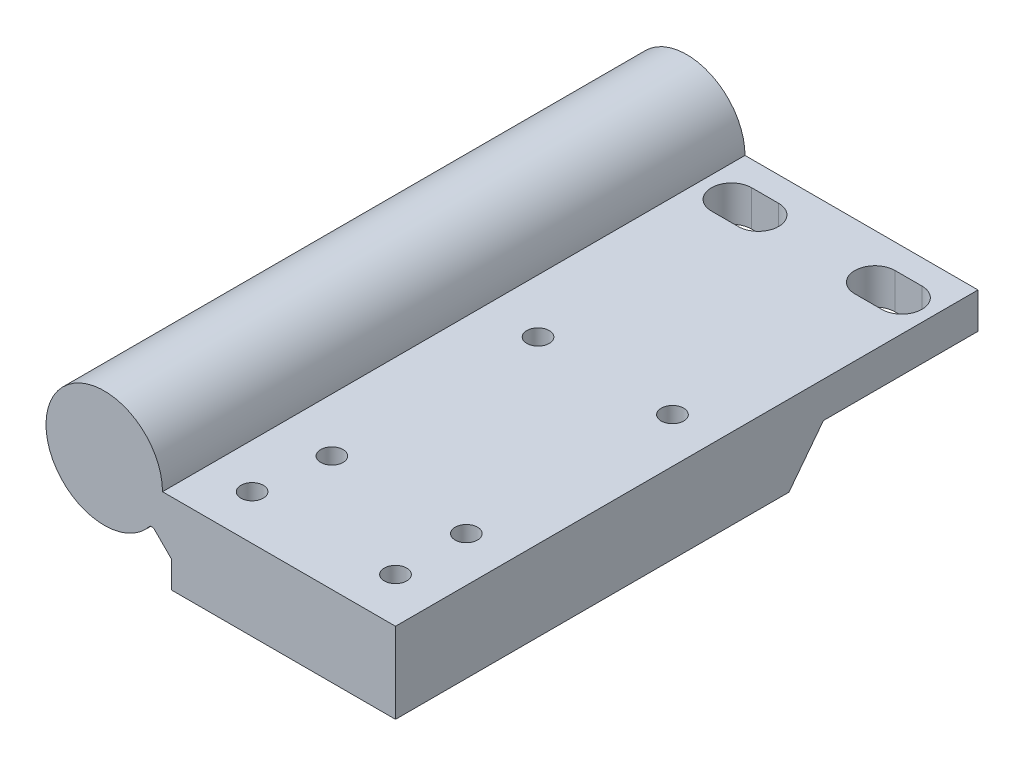
SolidWorks part; units mm, degrees
ref_plane "Спереди" through (0, 0, 0) normal (0, 0, 1) x (1, 0, 0)
ref_plane "Сверху" through (0, 0, 0) normal (0, 1, 0) x (1, 0, 0)
ref_plane "Справа" through (0, 0, 0) normal (1, 0, 0) x (0, 0, -1)
other "Configuration Table"
sketch "Эскиз1" plane through (0, 0, 0) normal (0, 0, 1) x (1, 0, 0)
  line L0 (5.1235, -4) -> (32.5, -4)
  line L1 (32.5, -4) -> (32.5, 0)
  line L2 (32.5, 0) -> (6.5, 0)
  circle A0 centre (0, 0) radius 4.1
  arc A1 (6.5, 0) -> (5.1235, -4) centre (0, 0) ccw
  circle A2 centre (39, 0) radius 6.5 construction
  dimension "D1" = 8.2
  dimension "D2" = 13
  dimension "D3" = 26
  dimension "D7" = 13
  dimension "D4" = 4
  dimension "D5" = 6.5
  dimension "D6" = 32.5
extrude "Бобышка-Вытянуть1" add sketch "Эскиз1" along normal blind 65
sketch "Эскиз2" plane through (0, 0, 65) normal (0, 0, 1) x (1, 0, 0)
  circle A0 centre (0, 0) radius 4.9232
extrude "Бобышка-Вытянуть2" add sketch "Эскиз2" against normal blind 3
sketch "Эскиз3" plane through (0, 0, 0) normal (0, 1, 0) x (1, 0, 0)
  line L0 (10, -7.25) -> (13, -7.25)
  line L1 (10, -2.75) -> (13, -2.75)
  line L6 (26, -2.75) -> (29, -2.75)
  line L7 (26, -7.25) -> (29, -7.25)
  line L8 (32.5, -65) -> (6.5, -65) construction
  line L9 (6.5, -65) -> (6.5, 0) construction
  line L11 (32.5, -65) -> (32.5, 0) construction
  arc A4 (10, -2.75) -> (10, -7.25) centre (10, -5) ccw
  arc A5 (29, -7.25) -> (29, -2.75) centre (29, -5) ccw
  arc A6 (13, -7.25) -> (13, -2.75) centre (13, -5) ccw
  arc A7 (26, -2.75) -> (26, -7.25) centre (26, -5) ccw
  circle A8 centre (11.5, -60) radius 1.25
  circle A9 centre (27.5, -60) radius 1.25
  point P23 (27.5, -7.25)
  point P25 (11.5, -7.25)
  dimension "D1" = 4.5
  dimension "D2" = 4.5
  dimension "D3" = 60
  dimension "D5" = 2.5
  dimension "D7" = 4.5
  dimension "D8" = 4.5
  dimension "D11" = 2.5
  dimension "D4" = 3.5
  dimension "D6" = 3.5
  dimension "D9" = 3
  dimension "D10" = 3
  dimension "D12" = 5
extrude "Вырез-Вытянуть1" cut sketch "Эскиз3" against normal blind 13
ref_plane "Плоскость1" through (20, 0, 0) normal (1, 0, 0) x (0, 0, -1)
sketch "Эскиз4" plane through (20, 0, 0) normal (1, 0, 0) x (0, 0, -1)
  line L0 (-17.25, -4) -> (-21.0942, -9)
  line L1 (-62, -4) -> (158, -4) construction
  line L2 (-21.0942, -9) -> (-65, -9)
  line L3 (-65, -9) -> (-65, -4)
  line L4 (-65, -4) -> (-17.25, -4)
  line L5 (-7.25, -4) -> (-7.25, 0) construction
  dimension "D1" = 10
  dimension "D2" = 5
extrude "Бобышка-Вытянуть3" add sketch "Эскиз4" along normal blind 12.5 and the other way blind 12.5
chamfer "Фаска4" distance 2 angle 45 1 edges at (7.5, -4, 41.125)
sketch "Эскиз5" plane through (0, -9, 0) normal (0, -1, 0) x (1, 0, 0)
  line L0 (7.5, 65) -> (32.5, 65) construction
  line L1 (7.5, 21.0942) -> (32.5, 21.0942) construction
  line L2 (7.5, 65) -> (7.5, 21.0942) construction
  line L3 (32.5, 65) -> (32.5, 21.0942) construction
  circle A0 centre (27.5, 29.0942) radius 1.25
  circle A1 centre (12.5, 29.0942) radius 1.25
  circle A2 centre (27.5, 52.0942) radius 1.25
  circle A3 centre (12.5, 52.0942) radius 1.25
  dimension "D1" = 2.5
  dimension "D2" = 2.5
  dimension "D3" = 2.5
  dimension "D4" = 2.5
  dimension "D5" = 12.9058
  dimension "D6" = 8
  dimension "D7" = 5
  dimension "D8" = 5
  dimension "D9" = 5
  dimension "D10" = 8
  dimension "D11" = 12.9058
extrude "Вырез-Вытянуть2" cut sketch "Эскиз5" against normal blind 10
